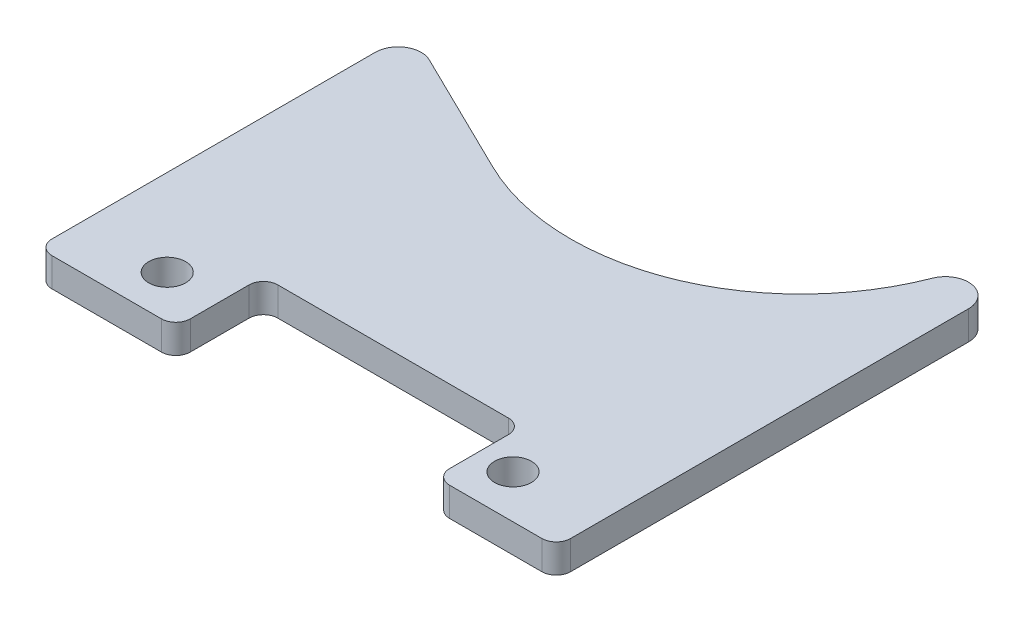
SolidWorks part; units mm, degrees
ref_plane "Front Plane" through (0, 0, 0) normal (0, 0, 1) x (1, 0, 0)
ref_plane "Top Plane" through (0, 0, 0) normal (0, 1, 0) x (1, 0, 0)
ref_plane "Right Plane" through (0, 0, 0) normal (1, 0, 0) x (0, 0, -1)
sketch "Sketch1" plane through (0, 0, 0) normal (0, 1, 0) x (1, 0, 0)
  line L1 (-28.575, 30.1625) -> (28.575, 30.1625)
  line L2 (-28.575, 30.1625) -> (-28.575, -30.1625)
  line L3 (-28.575, -30.1625) -> (28.575, -30.1625)
  line L4 (28.575, 30.1625) -> (28.575, -30.1625)
  line L5 (-28.575, 30.1625) -> (28.575, -30.1625) construction
  line L6 (-28.575, -30.1625) -> (28.575, 30.1625) construction
  point P0 (0, 0)
  dimension "D1" = 57.15
  dimension "D2" = 60.325
extrude "Boss-Extrude1" add sketch "Sketch1" along normal blind 3.175
sketch "Sketch2" plane through (0, 0, 0) normal (0, -1, 0) x (-1, 0, 0)
  line L0 (28.575, -30.1625) -> (-28.575, -30.1625) construction
  line L1 (-19.05, -25.4) -> (-28.575, -25.4) construction
  line L2 (-28.575, -30.1625) -> (-28.575, 30.1625) construction
  line L3 (19.05, -25.4) -> (28.575, -25.4) construction
  line L4 (28.575, 30.1625) -> (28.575, -30.1625) construction
  circle A0 centre (-19.05, -25.4) radius 2.032
  circle A1 centre (19.05, -25.4) radius 2.032
  dimension "D2" = 4.064
  dimension "D1" = 4.7625
  dimension "D3" = 38.1
extrude "Cut-Extrude1" cut sketch "Sketch2" against normal through all
sketch "Sketch3" plane through (0, 3.175, 0) normal (0, 1, 0) x (1, 0, 0)
  line L0 (-28.575, -30.1625) -> (28.575, -30.1625) construction
  line L1 (-13.335, -30.1625) -> (15.24, -30.1625)
  line L2 (-13.335, -30.1625) -> (-13.335, -20.5105)
  line L3 (-13.335, -20.5105) -> (15.24, -20.5105)
  line L4 (15.24, -30.1625) -> (15.24, -20.5105)
  line L5 (-28.575, 30.1625) -> (-28.575, -30.1625) construction
  dimension "D1" = 15.24
  dimension "D2" = 28.575
  dimension "D3" = 9.652
extrude "Cut-Extrude2" cut sketch "Sketch3" against normal through all
fillet "Fillet1" radius 1.5875 6 edges at (-28.575, 1.5875, 30.1625) (-13.335, 1.5875, 30.1625) (-13.335, 1.5875, 20.5105) (15.24, 1.5875, 20.5105) (15.24, 1.5875, 30.1625) (28.575, 1.5875, 30.1625)
sketch "Sketch5" plane through (0, 3.175, 0) normal (0, 1, 0) x (1, 0, 0)
  line L4 (-11.1723, 2.589) -> (-28.575, 11.1125)
  line L5 (-28.575, 30.1625) -> (-28.575, -28.575) construction
  line L6 (23.9755, 17.0135) -> (28.575, 30.1625)
  line L7 (-28.575, 11.1125) -> (-28.575, 30.1625)
  line L8 (-28.575, 30.1625) -> (28.575, 30.1625)
  line L9 (28.575, -28.575) -> (28.575, 30.1625) construction
  line L10 (-26.9875, -30.1625) -> (-14.9225, -30.1625) construction
  arc A1 (-11.1723, 2.589) -> (23.9755, 17.0135) centre (0, 25.4) ccw
  point P9 (29.6238, 29.2467)
  point P15 (28.575, 30.5302)
  point P16 (-28.575, 30.8062)
  point P17 (-28.575, 28.2503)
  point P18 (-28.575, 29.2822)
  point P19 (-28.575, 30.2792)
  dimension "D1" = 50.8
  dimension "D2" = 25.4
  dimension "D3" = 60.325
  dimension "D4" = 19.05
extrude "Cut-Extrude4" cut sketch "Sketch5" against normal through all
fillet "Fillet2" radius 2.54 2 edges at (28.575, 1.5875, -30.1625) (-28.575, 1.5875, -11.1125)
